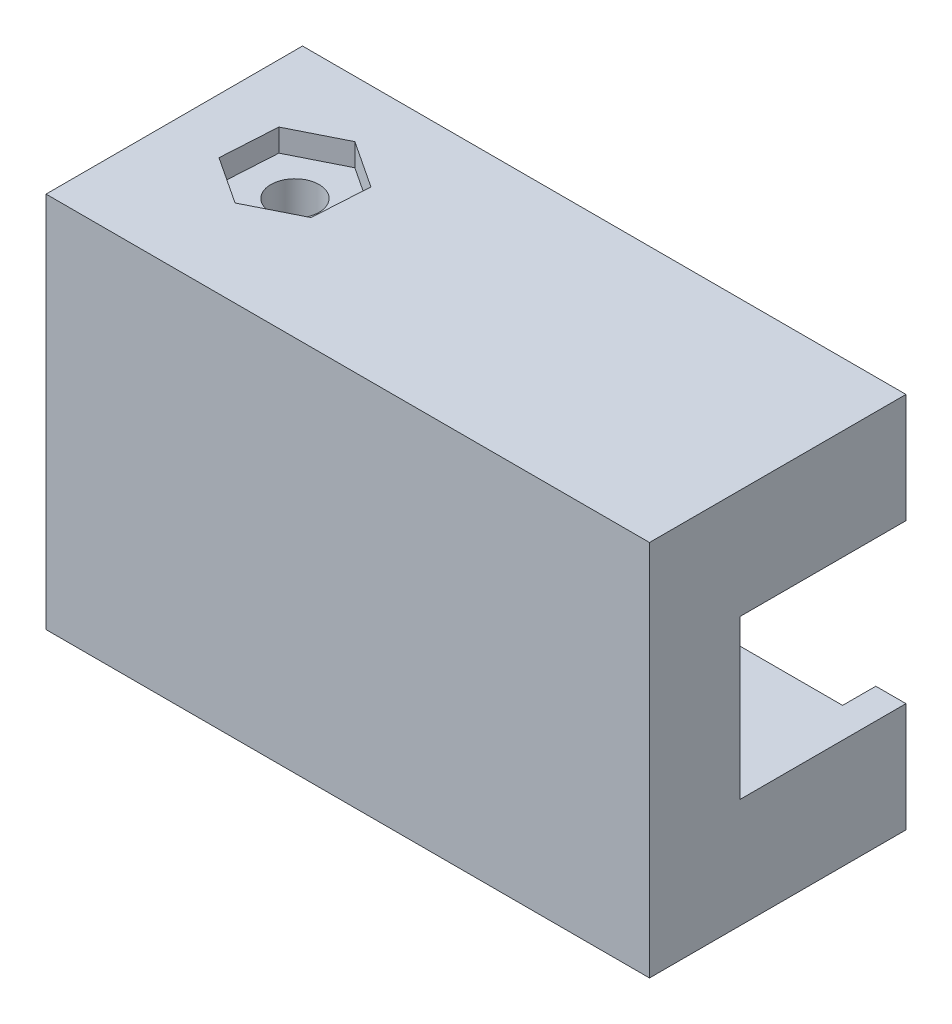
SolidWorks part; units mm, degrees
material "ABS"
ref_plane "Front Plane" through (0, 0, 0) normal (0, 0, 1) x (1, 0, 0)
ref_plane "Top Plane" through (0, 0, 0) normal (0, 1, 0) x (1, 0, 0)
ref_plane "Right Plane" through (0, 0, 0) normal (1, 0, 0) x (0, 0, -1)
sketch "Sketch1" plane through (0, 0, 0) normal (0, 0, 1) x (1, 0, 0)
  line L0 (-20, 12.5) -> (20, 12.5) construction
  line L1 (0, 5.25) -> (0, -5.25) construction
  line L2 (-20, -12.5) -> (20, -12.5) construction
  line L3 (-20, -12.5) -> (-20, 12.5) construction
  line L4 (-20, 12.5) -> (20, 12.5)
  line L5 (20, -12.5) -> (20, 12.5)
  line L6 (-20, -12.5) -> (20, -12.5)
  line L7 (-20, -12.5) -> (-20, 12.5)
  line L8 (-20, -5.25) -> (20, -5.25)
  line L9 (-20, -5.25) -> (20, -5.25) construction
  line L10 (-20, 5.25) -> (20, 5.25)
  line L11 (-20, 5.25) -> (20, 5.25) construction
  point P3 (0, 0)
  dimension "D1" = 10.5
extrude "Boss-Extrude1" add sketch "Sketch1" along normal blind 11 contours L5 L4 L7 L10 | L7 L6 L5 L8 region at (0, 8.875, 0) region at (0, -8.875, 0)
extrude "Boss-Extrude2" add sketch "Sketch1<3>" along normal blind 6 from surface contours L10 L7 L8 L5 | L5 L4 L7 L10 | L7 L6 L5 L8 region at (0, 8.875, 0) region at (0, 0, 0) region at (0, -8.875, 0) starting at face at (0, -8.875, 11)
sketch "Sketch1<3>" plane through (0, 0, 0) normal (0, 0, 1) x (1, 0, 0) same geometry as "Sketch1"
sketch "Sketch3" plane through (0, 0, 11) normal (0, 0, -1) x (-1, 0, 0)
  line L0 (-20, 0) -> (-14, 0) construction
  line L1 (-20, 5.25) -> (-20, -5.25) construction
  circle A0 centre (-14, 0) radius 4.25
  dimension "D1" = 8.5
  dimension "D2" = 6
extrude "Cut-Extrude1" cut sketch "Sketch3" against normal blind 5
sketch "Sketch4" plane through (0, -12.5, 0) normal (0, -1, 0) x (1, 0, 0)
  line L1 (-20, 17) -> (-20, 0) construction
  circle A0 centre (-13, 7.5) radius 1.6
  dimension "D1" = 3.2
  dimension "D2" = 3.5
  dimension "D3" = 7
extrude "Cut-Extrude2" cut sketch "Sketch4" against normal through all
sketch "Sketch5" plane through (0, 12.5, 0) normal (0, 1, 0) x (1, 0, 0)
  line L1 (-9.868, -9.5674) -> (-9.6436, -5.8213)
  line L2 (-9.6436, -5.8213) -> (-12.7756, -3.7539)
  line L3 (-12.7756, -3.7539) -> (-16.132, -5.4326)
  line L4 (-16.132, -5.4326) -> (-16.3564, -9.1787)
  line L5 (-16.3564, -9.1787) -> (-13.2244, -11.2461)
  line L6 (-13.2244, -11.2461) -> (-9.868, -9.5674)
  circle A0 centre (-13, -7.5) radius 3.25 construction
  dimension "D1" = 6.5
extrude "Cut-Extrude3" cut sketch "Sketch5" against normal blind 1.5
sketch "Sketch6" plane through (0, 0, 0) normal (0, 0, -1) x (-1, 0, 0)
  circle A0 centre (8, -8.875) radius 2.475
  circle A2 centre (0, 8.875) radius 2.475
  dimension "D1" = 4.95
extrude "Cut-Extrude4" cut sketch "Sketch6" against normal blind 4
sketch "Sketch7" plane through (0, 0, 0) normal (0, 0, -1) x (-1, 0, 0)
  line L0 (18, 5.25) -> (18, 11.5)
  line L1 (20, 5.25) -> (-20, 5.25) construction
  line L2 (18, 11.5) -> (-18, 11.5)
  line L3 (-18, 11.5) -> (-18, 5.25)
  line L4 (-18, 5.25) -> (18, 5.25)
  line L5 (20, 0) -> (-20, 0) construction
  line L6 (20, 5.25) -> (20, -5.25) construction
  line L7 (-20, 5.25) -> (-20, -5.25) construction
  line L8 (20, 5.25) -> (20, 12.5) construction
  line L9 (20, 12.5) -> (-20, 12.5) construction
  line L10 (-20, 5.25) -> (-20, 12.5) construction
  line L11 (-18, -11.5) -> (-18, -5.25)
  line L12 (18, -11.5) -> (-18, -11.5)
  line L13 (18, -5.25) -> (18, -11.5)
  line L14 (-18, -5.25) -> (18, -5.25)
  dimension "D1" = 2
  dimension "D2" = 1
  dimension "D3" = 2
extrude "Cut-Extrude5" cut sketch "Sketch7" against normal blind 2.2
